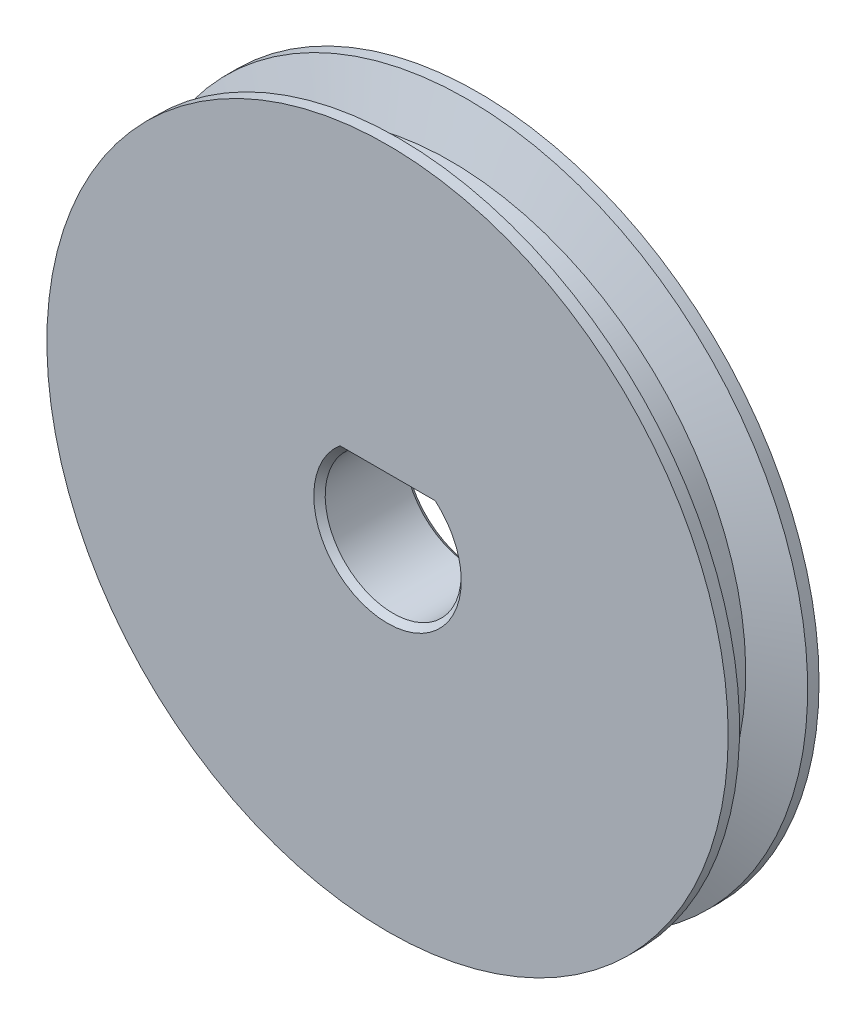
SolidWorks part; units mm, degrees
material "6061-T6 (SS)"
ref_plane "Front Plane" through (0, 0, 0) normal (0, 0, 1) x (1, 0, 0)
ref_plane "Top Plane" through (0, 0, 0) normal (0, 1, 0) x (1, 0, 0)
ref_plane "Right Plane" through (0, 0, 0) normal (1, 0, 0) x (0, 0, -1)
sketch "Sketch1" plane through (0, 0, 0) normal (0, 0, 1) x (1, 0, 0)
  circle A0 centre (0, 0) radius 47.625
  circle A1 centre (0, 0) radius 9.5123
  dimension "D1" = 95.25
  dimension "D2" = 19.0246
extrude "Extrude1" add sketch "Sketch1" along normal mid plane 12.7
sketch "Sketch2" plane through (0, 0, 0) normal (1, 0, 0) x (0, 0, -1)
  line L0 (-4.7625, 47.625) -> (4.7625, 47.625)
  line L2 (4.7625, 47.625) -> (2.4513, 41.275)
  line L3 (2.4513, 41.275) -> (-2.4513, 41.275)
  line L4 (-2.4513, 41.275) -> (-4.7625, 47.625)
  line L5 (-6.35, 0) -> (6.35, 0) construction
  line L6 (-6.35, 47.625) -> (-6.35, -47.625) construction
  line L7 (6.35, -47.625) -> (6.35, 47.625) construction
  point P2 (0, 47.625)
  point P5 (0, 41.275)
  dimension "D1" = 47.625
  dimension "D2" = 6.35
  dimension "D3" = 9.525
  dimension "D4" = 40
revolve "Cut-Revolve1" cut sketch "Sketch2" angle 360 about L5
sketch "Sketch3" plane through (0, 0, -6.35) normal (0, 0, -1) x (-1, 0, 0)
  line L0 (-6.3595, 7.0739) -> (6.3595, 7.0739)
  line L1 (0, 7.0739) -> (0, -9.5123) construction
  circle A0 centre (0, 0) radius 9.5123 construction
  circle A2 centre (0, 0) radius 9.5123
  arc A3 (6.3595, 7.0739) -> (-6.3595, 7.0739) centre (0, 0) ccw
  dimension "D1" = 16.5862
  dimension "D2" = 0
extrude "Boss-Extrude1" add sketch "Sketch3" against normal up to surface (12.7 mm away) up to face at (47.625, 0, 6.35)
chamfer "Chamfer3" distance 0.795 angle 45 4 edges at (0, -9.5123, 6.35) (0, 7.0739, 6.35) (0, 7.0739, -6.35) (0, -9.5123, -6.35)
